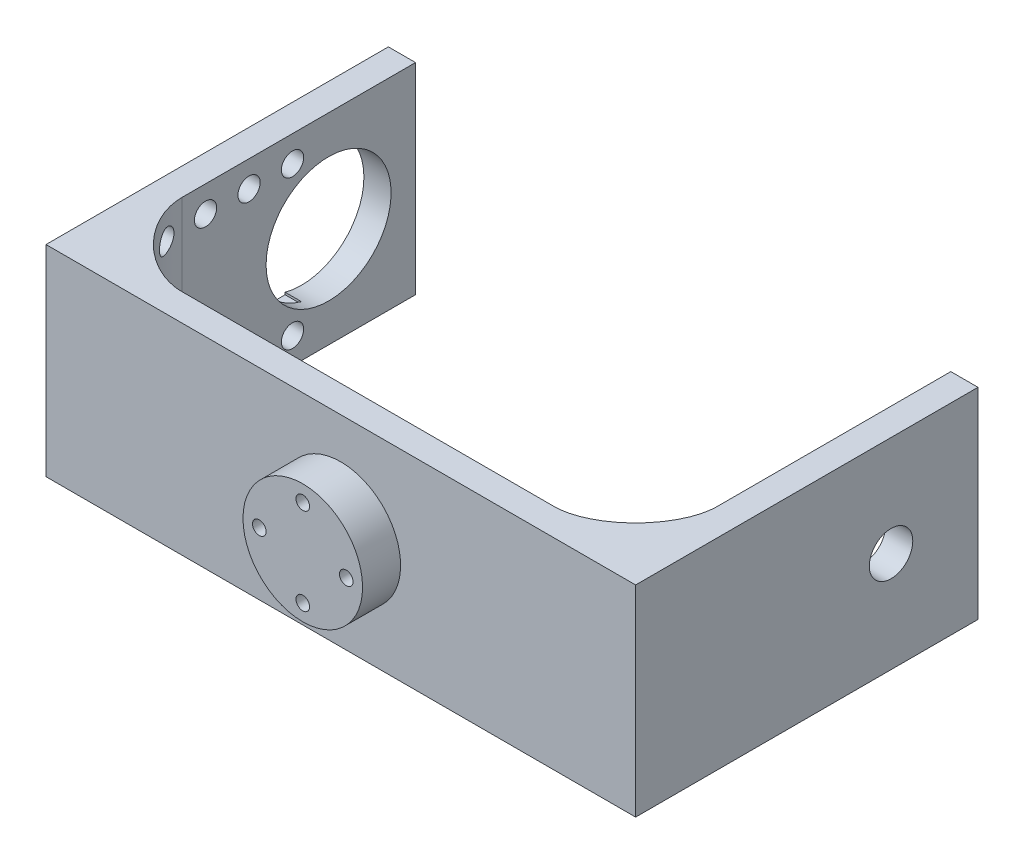
SolidWorks part; units mm, degrees
ref_plane "Front Plane" through (0, 0, 0) normal (0, 0, 1) x (1, 0, 0)
ref_plane "Top Plane" through (0, 0, 0) normal (0, 1, 0) x (1, 0, 0)
ref_plane "Right Plane" through (0, 0, 0) normal (1, 0, 0) x (0, 0, -1)
sketch "Sketch2" plane through (0, 0, 0) normal (0, 1, 0) x (1, 0, 0)
  line L0 (0, 0) -> (0, -63)
  line L1 (0, -63) -> (108.5, -63)
  line L2 (108.5, -63) -> (108.5, 0)
  line L3 (108.5, 0) -> (103.5, 0)
  line L4 (103.5, 0) -> (103.5, -58)
  line L5 (103.5, -58) -> (5, -58)
  line L6 (5, -58) -> (5, 0)
  line L7 (5, 0) -> (0, 0)
  dimension "D1" = 108.5
  dimension "D2" = 98.5
  dimension "D3" = 5
  dimension "D5" = 58
  dimension "D6" = 63
extrude "Boss-Extrude3" add sketch "Sketch2" along normal blind 37
sketch "Sketch3" plane through (0, 0, 0) normal (-1, 0, 0) x (0, 0, 1)
  line L0 (0, 0) -> (16, 0)
  line L1 (0, 0) -> (63, 0) construction
  line L4 (16, 18.5) -> (8, 18.5)
  circle A0 centre (16, 18.5) radius 11.5
  point P21 (16, 18.5)
  dimension "D2" = 8
  dimension "D1" = 16
sketch "Sketch4" plane through (0, 0, 0) normal (-1, 0, 0) x (0, 0, 1)
  line L0 (0, 18.5) -> (63, 18.5)
  line L1 (0, 37) -> (0, 0) construction
  line L3 (63, 37) -> (63, 0) construction
  circle A0 centre (22.64, 32.19) radius 1.25
  circle A1 centre (30.64, 32.19) radius 1.25
  circle A2 centre (38.64, 32.19) radius 1.25
  circle A3 centre (46.64, 32.19) radius 1.25
  circle A4 centre (46.64, 4.81) radius 1.25
  circle A5 centre (38.64, 4.81) radius 1.25
  circle A6 centre (30.64, 4.81) radius 1.25
  circle A7 centre (22.64, 4.81) radius 1.25
  circle A8 centre (52.14, 26.69) radius 1.25
  circle A9 centre (52.14, 10.31) radius 1.25
  dimension "D3" = 2.5
  dimension "D6" = 2.5
  dimension "D7" = 2.5
  dimension "D1" = 4
extrude "Cut-Extrude3" cut sketch "Sketch3" against normal up to next
extrude "Cut-Extrude4" cut sketch "Sketch4" against normal up to next contours A0 | A1 | A2 | A3 | A4 | A5 | A6 | A7 | A8 | A9
sketch "Sketch6" plane through (0, 0, 0) normal (-1, 0, 0) x (0, 0, 1)
  line L0 (19, 30) -> (19, 7)
  line L1 (67.598, 0) -> (67.598, 37)
  line L3 (0, 0) -> (63, 0) construction
  line L4 (57, 7) -> (57, 30)
  line L5 (0, 37) -> (63, 37) construction
  line L6 (67.598, 37) -> (67.598, 18.5)
  line L7 (67.598, 18.5) -> (51.9967, 18.5)
  line L8 (57, 30) -> (19, 30)
  line L9 (57, 7) -> (19, 7)
  dimension "D1" = 23
extrude "Cut-Extrude6" cut sketch "Sketch6" against normal blind 3
sketch "Sketch10" plane through (0, 0, 57) normal (0, 0, -1) x (-1, 0, 0)
  line L4 (0, 7) -> (0, 30)
  line L5 (0, 30) -> (-3, 30)
  line L6 (-3, 30) -> (-3, 7)
  line L7 (-3, 7) -> (0, 7)
  line L8 (0, 7) -> (0, 30)
  line L9 (0, 30) -> (-3, 30)
  line L10 (-3, 30) -> (-3, 7)
  line L11 (-3, 7) -> (0, 7)
  dimension "D1" = 0
extrude "Boss-Extrude5" add sketch "Sketch10" along normal blind 7.5
sketch "Sketch11" plane through (3, 0, 0) normal (1, 0, 0) x (0, 0, -1)
  circle A0 centre (-52.14, 26.69) radius 1.25 construction
  circle A1 centre (-52.14, 10.31) radius 1.25 construction
  circle A2 centre (-52.14, 26.69) radius 1.25
  circle A3 centre (-52.14, 10.31) radius 1.25
extrude "Cut-Extrude11" cut sketch "Sketch11" against normal up to next
sketch "Sketch12" plane through (5, 0, 0) normal (1, 0, 0) x (0, 0, -1)
  circle A0 centre (-52.14, 26.69) radius 2.05
  circle A1 centre (-46.64, 32.19) radius 2.05
  circle A2 centre (-38.64, 32.19) radius 2.05
  circle A3 centre (-30.64, 32.19) radius 2.05
  circle A4 centre (-22.64, 32.19) radius 2.05
  circle A5 centre (-30.64, 4.81) radius 2.05
  circle A6 centre (-22.64, 4.81) radius 2.05
  circle A7 centre (-38.64, 4.81) radius 2.05
  circle A8 centre (-46.64, 4.81) radius 2.05
  circle A9 centre (-52.14, 10.31) radius 2.05
  dimension "D1" = 4.1
  dimension "D2" = 4.1
  dimension "D3" = 4.1
  dimension "D4" = 4.1
  dimension "D5" = 4.1
  dimension "D6" = 4.1
  dimension "D7" = 4.1
  dimension "D8" = 4.1
  dimension "D9" = 4.1
  dimension "D10" = 4.1
extrude "Cut-Extrude12" cut sketch "Sketch12" against normal blind 3
sketch "Sketch13" plane through (108.5, 0, 0) normal (1, 0, 0) x (0, 0, -1)
  circle A0 centre (-16, 18.5) radius 4
  dimension "D1" = 8
extrude "Cut-Extrude13" cut sketch "Sketch13" against normal up to next
fillet "Fillet5" radius 15 2 edges at (103.5, 18.5, 58) (5, 18.5, 58)
sketch "Sketch14" plane through (0, 0, 63) normal (0, 0, 1) x (1, 0, 0)
  line L0 (54.25, 37) -> (54.25, 0)
  line L1 (0, 37) -> (108.5, 37) construction
  line L2 (0, 0) -> (108.5, 0) construction
  circle A0 centre (54.25, 18.5) radius 11
  circle A1 centre (62.25, 18.5) radius 1.25
  circle A2 centre (54.25, 10.5) radius 1.25
  circle A3 centre (46.25, 18.5) radius 1.25
  circle A4 centre (54.25, 26.5) radius 1.25
  point P19 (54.25, 18.5)
  dimension "D1" = 22
  dimension "D3" = 2.5
  dimension "D2" = 8
  dimension "D4" = 4
extrude "Boss-Extrude6" add sketch "Sketch14" along normal blind 7 contours A4 L0 A0 A2 A3 | A4 L0 A2 A0 A1
sketch "Sketch15" plane through (0, 0, 70) normal (0, 0, 1) x (1, 0, 0)
  circle A0 centre (54.25, 10.5) radius 1.25 construction
  circle A1 centre (46.25, 18.5) radius 1.25 construction
  circle A2 centre (54.25, 26.5) radius 1.25 construction
  circle A3 centre (62.25, 18.5) radius 1.25 construction
  circle A4 centre (54.25, 10.5) radius 1.25
  circle A5 centre (46.25, 18.5) radius 1.25
  circle A6 centre (54.25, 26.5) radius 1.25
  circle A7 centre (62.25, 18.5) radius 1.25
extrude "Cut-Extrude14" cut sketch "Sketch15" against normal up to next
sketch "Sketch16" plane through (0, 0, 58) normal (0, 0, -1) x (-1, 0, 0)
  circle A0 centre (-46.25, 18.5) radius 2.55
  circle A1 centre (-54.25, 10.5) radius 2.55
  circle A2 centre (-62.25, 18.5) radius 2.55
  circle A3 centre (-54.25, 26.5) radius 2.55
  dimension "D1" = 5.1
  dimension "D2" = 5.1
  dimension "D3" = 5.1
  dimension "D4" = 5.1
extrude "Cut-Extrude15" cut sketch "Sketch16" against normal blind 4
